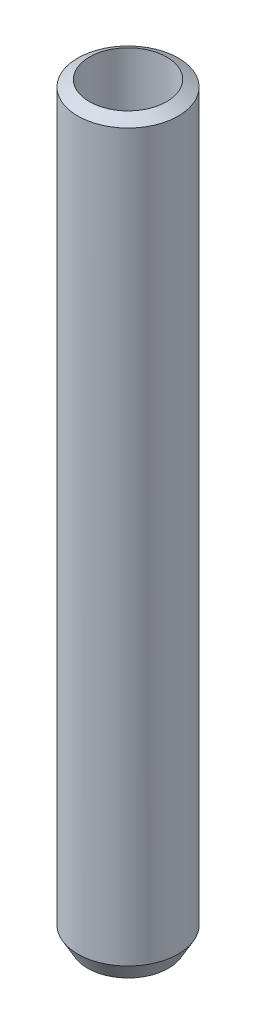
SolidWorks part; units mm, degrees
ref_plane "Front Plane" through (0, 0, 0) normal (0, 0, 1) x (1, 0, 0)
ref_plane "Top Plane" through (0, 0, 0) normal (0, 1, 0) x (1, 0, 0)
ref_plane "Right Plane" through (0, 0, 0) normal (1, 0, 0) x (0, 0, -1)
sketch "Sketch1" plane through (0, 0, 0) normal (0, 1, 0) x (1, 0, 0)
  circle A0 centre (0, 0) radius 15
  dimension "SHAFT_OD" = 30
extrude "Boss-Extrude1" add sketch "Sketch1" along normal blind 224.6429
sketch "Sketch2" plane through (0, 0, 0) normal (0, 1, 0) x (1, 0, 0)
  circle A0 centre (0, 0) radius 11.5383
  dimension "BORE_D" = 23.0767
extrude "Cut-Extrude1" cut sketch "Sketch2" along normal through all
chamfer "Chamfer1" distance 2.9682 angle 60.204 2 edges at (0, 224.6429, 15) (0, 0, 15) first distance on face at (0, 224.6429, 15) first distance on face at (0, 0, 11.5383)
